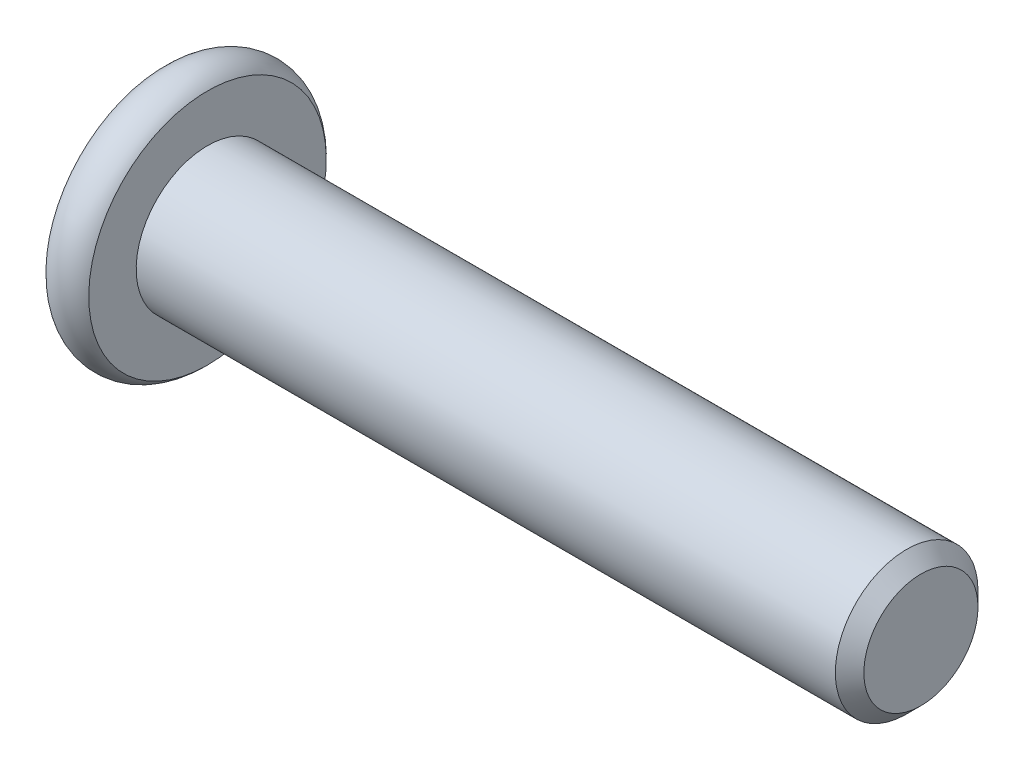
SolidWorks part; units mm, degrees
material "Plain Carbon Steel"
ref_plane "Front Plane" through (0, 0, 0) normal (0, 0, 1) x (1, 0, 0)
ref_plane "Top Plane" through (0, 0, 0) normal (0, 1, 0) x (1, 0, 0)
ref_plane "Right Plane" through (0, 0, 0) normal (1, 0, 0) x (0, 0, -1)
other "M5 x 15"
sketch "Sketch2" plane through (0, 0, 0) normal (1, 0, 0) x (0, 0, -1)
  circle A0 centre (0, 0) radius 2.5
  dimension "D1" = 5
extrude "Boss-Extrude1" add sketch "Sketch2" against normal blind 25
chamfer "Chamfer1" distance 0.5 angle 45 1 edges at (0, 0, -2.5)
sketch "Sketch6" plane through (0, 0, 0) normal (0, 0, 1) x (1, 0, 0)
  line L0 (-26.5, 0) -> (-26.5, 4.1614)
  line L1 (-26.5, 0) -> (-25, 0)
  line L2 (-25.75, 0) -> (-25.75, 3.5) construction
  line L6 (-25, 4.1614) -> (-25, 0)
  line L8 (-25, 0) -> (-14.6471, 0) construction
  line L10 (-25, 2.5) -> (-25, -2.5) construction
  arc A0 (-26.5, 4.1614) -> (-25, 4.1614) centre (-25.75, 3.5) cw
  dimension "D3" = 1
  dimension "D1" = 1.5
  dimension "D2" = 9
revolve "Revolve1" add sketch "Sketch6" angle 360 about L8
sketch "Sketch7" plane through (-26.5, 0, 0) normal (-1, 0, 0) x (0, 0, 1)
  line L1 (0, 1.7321) -> (-1.5, 0.866)
  line L2 (-1.5, 0.866) -> (-1.5, -0.866)
  line L3 (-1.5, -0.866) -> (0, -1.7321)
  line L4 (0, -1.7321) -> (1.5, -0.866)
  line L5 (1.5, -0.866) -> (1.5, 0.866)
  line L6 (1.5, 0.866) -> (0, 1.7321)
  circle A0 centre (0, 0) radius 1.5 construction
  dimension "D1" = 3
extrude "Cut-Extrude1" cut sketch "Sketch7" against normal blind 2.3
sketch "Sketch8" plane through (-26.5, 0, 0) normal (-1, 0, 0) x (0, 0, 1)
  circle A0 centre (0, 0) radius 1.7821
  dimension "D1" = 0.05
extrude "Cut-Extrude2" cut sketch "Sketch8" against normal blind 1 draft 45
ref_axis "Axis1" through (-25, 0, 0) along (1, 0, 0)
